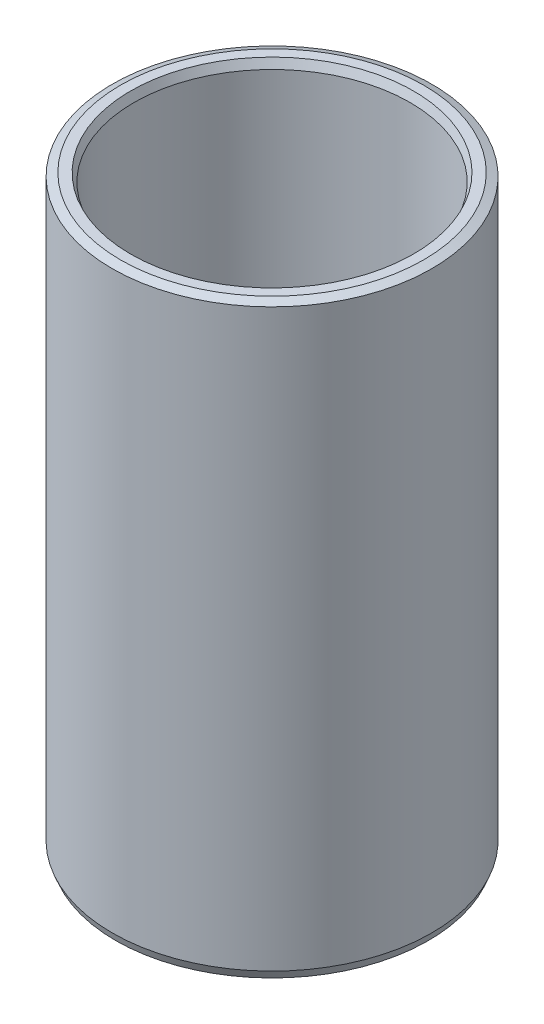
SolidWorks part; units mm, degrees
ref_plane "Front Plane" through (0, 0, 0) normal (0, 0, 1) x (1, 0, 0)
ref_plane "Top Plane" through (0, 0, 0) normal (0, 1, 0) x (1, 0, 0)
ref_plane "Right Plane" through (0, 0, 0) normal (1, 0, 0) x (0, 0, -1)
sketch "Sketch1" plane through (0, 0, 0) normal (0, 1, 0) x (1, 0, 0)
  circle A0 centre (0, 0) radius 60
  dimension "SLEEVE_OD" = 120
extrude "Boss-Extrude1" add sketch "Sketch1" along normal blind 220.3822
sketch "Sketch2" plane through (0, 0, 0) normal (0, 1, 0) x (1, 0, 0)
  circle A0 centre (0, 0) radius 51.8202
  dimension "BORE_D" = 103.6405
extrude "Cut-Extrude1" cut sketch "Sketch2" along normal through all
chamfer "Chamfer1" distance 1.2662 angle 67.963 4 edges at (0, 220.3822, 51.8202) (0, 0, 51.8202) (0, 0, 60) (0, 220.3822, 60) first distance on face at (0, 220.3822, 51.8202) first distance on face at (0, 0, 51.8202) first distance on face at (0, 220.3822, 60)
